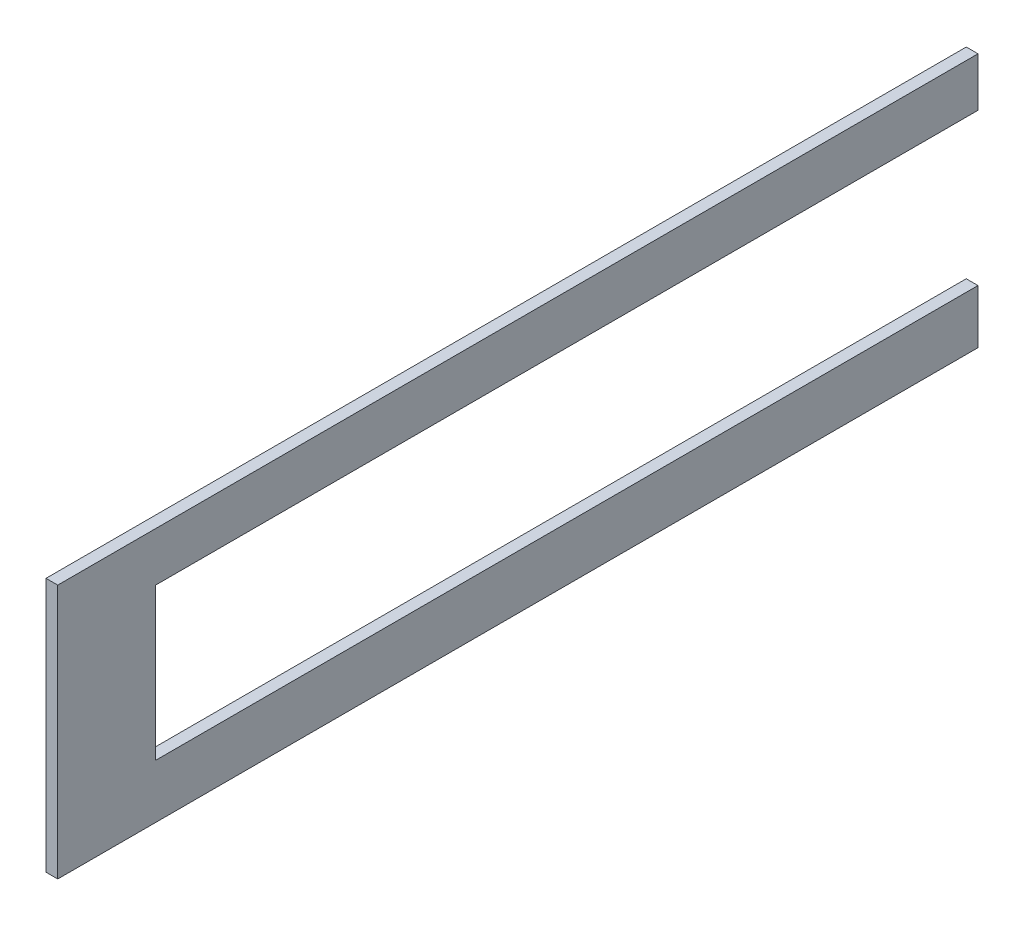
SolidWorks part; units mm, degrees
ref_plane "Front" through (0, 0, 0) normal (0, 0, 1) x (1, 0, 0)
ref_plane "Top" through (0, 0, 0) normal (0, 1, 0) x (1, 0, 0)
ref_plane "Right" through (0, 0, 0) normal (1, 0, 0) x (0, 0, -1)
sketch "Sketch1" plane through (0, 0, 0) normal (1, 0, 0) x (0, 0, -1)
  line L0 (470, 105) -> (470, 130)
  line L1 (0, 0) -> (470, 0)
  line L2 (0, 0) -> (0, 130)
  line L3 (0, 130) -> (470, 130)
  line L4 (470, 0) -> (470, 27.5)
  line L5 (470, 105) -> (50, 105)
  line L7 (470, 27.5) -> (50, 27.5)
  line L8 (50, 105) -> (50, 27.5)
  dimension "D1" = 420
  dimension "D2" = 130
  dimension "D3" = 27.5
  dimension "D4" = 25
  dimension "D5" = 50
extrude "Boss-Extrude1" add sketch "Sketch1" along normal blind 6
